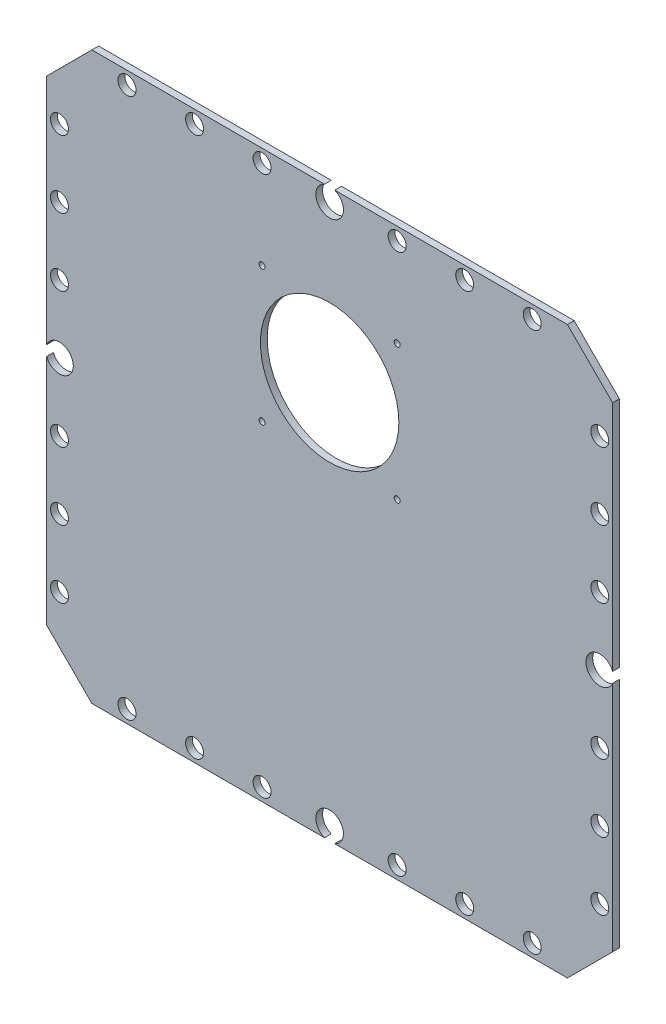
SolidWorks part; units mm, degrees
ref_plane "Front Plane" through (0, 0, 0) normal (0, 0, 1) x (1, 0, 0)
ref_plane "Top Plane" through (0, 0, 0) normal (0, 1, 0) x (1, 0, 0)
ref_plane "Right Plane" through (0, 0, 0) normal (1, 0, 0) x (0, 0, -1)
sketch "Sketch1" plane through (0, 0, 0) normal (0, 0, 1) x (1, 0, 0)
  line L0 (30.226, -4.826) -> (55.626, -4.826) construction
  line L1 (0, 0) -> (212.852, 0)
  line L2 (0, 0) -> (0, -212.852)
  line L3 (0, -212.852) -> (212.852, -212.852)
  line L4 (212.852, 0) -> (212.852, -212.852)
  line L5 (55.626, -4.826) -> (81.026, -4.826) construction
  line L6 (81.026, -4.826) -> (106.426, -4.826) construction
  line L7 (106.426, -4.826) -> (131.826, -4.826) construction
  line L8 (131.826, -4.826) -> (157.226, -4.826) construction
  line L9 (157.226, -4.826) -> (182.626, -4.826) construction
  line L10 (106.426, 0) -> (106.426, -212.852) construction
  line L11 (0, -106.426) -> (212.852, -106.426) construction
  line L12 (16.9978, 0) -> (0, -16.9978)
  line L13 (212.852, -16.9978) -> (195.8542, 0)
  line L14 (195.8542, -212.852) -> (212.852, -195.8542)
  line L15 (0, -195.8542) -> (16.9978, -212.852)
  line L17 (81.026, -38.2041) -> (131.826, -38.2042) construction
  line L18 (81.026, -38.2041) -> (81.026, -89.0042) construction
  line L19 (81.026, -89.0042) -> (131.826, -89.0042) construction
  line L20 (131.826, -38.2042) -> (131.826, -89.0042) construction
  line L21 (106.426, -89.0042) -> (106.426, -38.2041) construction
  line L22 (81.026, -63.6041) -> (131.826, -63.6041) construction
  circle A0 centre (30.226, -4.826) radius 3.38
  circle A1 centre (55.626, -4.826) radius 3.38
  circle A2 centre (81.026, -4.826) radius 3.38
  circle A3 centre (131.826, -4.826) radius 3.38
  circle A4 centre (157.226, -4.826) radius 3.38
  circle A5 centre (182.626, -4.826) radius 3.38
  circle A6 centre (106.426, -4.826) radius 5.1943
  circle A7 centre (208.026, -182.626) radius 3.38
  circle A8 centre (208.026, -157.226) radius 3.38
  circle A9 centre (208.026, -131.826) radius 3.38
  circle A10 centre (208.026, -106.426) radius 5.1943
  circle A11 centre (208.026, -81.026) radius 3.38
  circle A12 centre (208.026, -55.626) radius 3.38
  circle A13 centre (208.026, -30.226) radius 3.38
  circle A14 centre (30.226, -208.026) radius 3.38
  circle A15 centre (55.626, -208.026) radius 3.38
  circle A16 centre (81.026, -208.026) radius 3.38
  circle A17 centre (106.426, -208.026) radius 5.1943
  circle A18 centre (131.826, -208.026) radius 3.38
  circle A19 centre (157.226, -208.026) radius 3.38
  circle A20 centre (182.626, -208.026) radius 3.38
  circle A21 centre (4.826, -30.226) radius 3.38
  circle A22 centre (4.826, -55.626) radius 3.38
  circle A23 centre (4.826, -81.026) radius 3.38
  circle A24 centre (4.826, -106.426) radius 5.1943
  circle A25 centre (4.826, -131.826) radius 3.38
  circle A26 centre (4.826, -157.226) radius 3.38
  circle A27 centre (4.826, -182.626) radius 3.38
  circle A28 centre (106.426, -63.6041) radius 26.035
  circle A29 centre (81.026, -38.2041) radius 1.13
  circle A30 centre (131.826, -38.2042) radius 1.13
  circle A31 centre (131.826, -89.0042) radius 1.13
  circle A32 centre (81.026, -89.0042) radius 1.13
  point P14 (106.426, -106.426)
  point P69 (106.426, -106.426)
  point P78 (106.426, -106.426)
  dimension "D1" = 6.76
  dimension "D5" = 10.3886
  dimension "D13" = 52.07
  dimension "D14" = 2.26
  dimension "D2" = 30.226
  dimension "D3" = 25.4
  dimension "D4" = 4.826
  dimension "D6" = 212.852
  dimension "D7" = 212.852
  dimension "D9" = 45
  dimension "D10" = 24.0386
  dimension "D12" = 63.6041
  dimension "D15" = 50.8
  dimension "D8" = 4
  dimension "D11" = 4
extrude "Boss-Extrude1" add sketch "Sketch1" along normal blind 2.54 contours A24 L2 L3 A17 L4 A10 L1 A6 A27 A26 A25 A23 A22 A21 A20 A19 A18 A16 A15 A14 A13 A12 A11 A9 A8 A7 A5 region at (106.426, -108.6459, 0)
hole_wizard "#4-40 Tapped Hole1" positions "3DSketch1" profile "Sketch2" tap size "#4-40" standard "ANSI Inch" end condition through all
sketch3d "3DSketch1"
  line L0 (81.026, -38.2041, 2.54) -> (81.026, -38.2041, 0) construction
  line L1 (131.826, -38.2042, 2.54) -> (131.826, -38.2042, 0) construction
  line L2 (131.826, -89.0042, 2.54) -> (131.826, -89.0042, 0) construction
  line L3 (81.026, -89.0042, 2.54) -> (81.026, -89.0042, 0) construction
  point P0 (81.026, -38.2041, 2.54)
  point P4 (131.826, -38.2042, 2.54)
  point P8 (131.826, -89.0042, 2.54)
  point P12 (81.026, -89.0042, 2.54)
sketch "Sketch2" plane through (81.026, -38.2041, 2.54) normal (1, 0, 0) x (0, -1, 0)
  line L0 (0, 0) -> (0, 2.54)
  line L1 (0, 2.54) -> (1.1303, 2.54)
  line L2 (1.1303, 2.54) -> (1.1303, 0)
  line L5 (1.1303, 0) -> (0, 0)
  line L11 (0, -6.35) -> (0, 107.95) construction
  dimension "Thru Tap Drill Dia." = 2.2606
  dimension "Thru Tap Drill Depth" = 2.54
cosmetic thread "Hole Thread1" parameters "D2"=2.8448
cosmetic thread "Hole Thread2" parameters "D2"=2.8448
cosmetic thread "Hole Thread3" parameters "D2"=2.8448
cosmetic thread "Hole Thread4" parameters "D2"=2.8448
